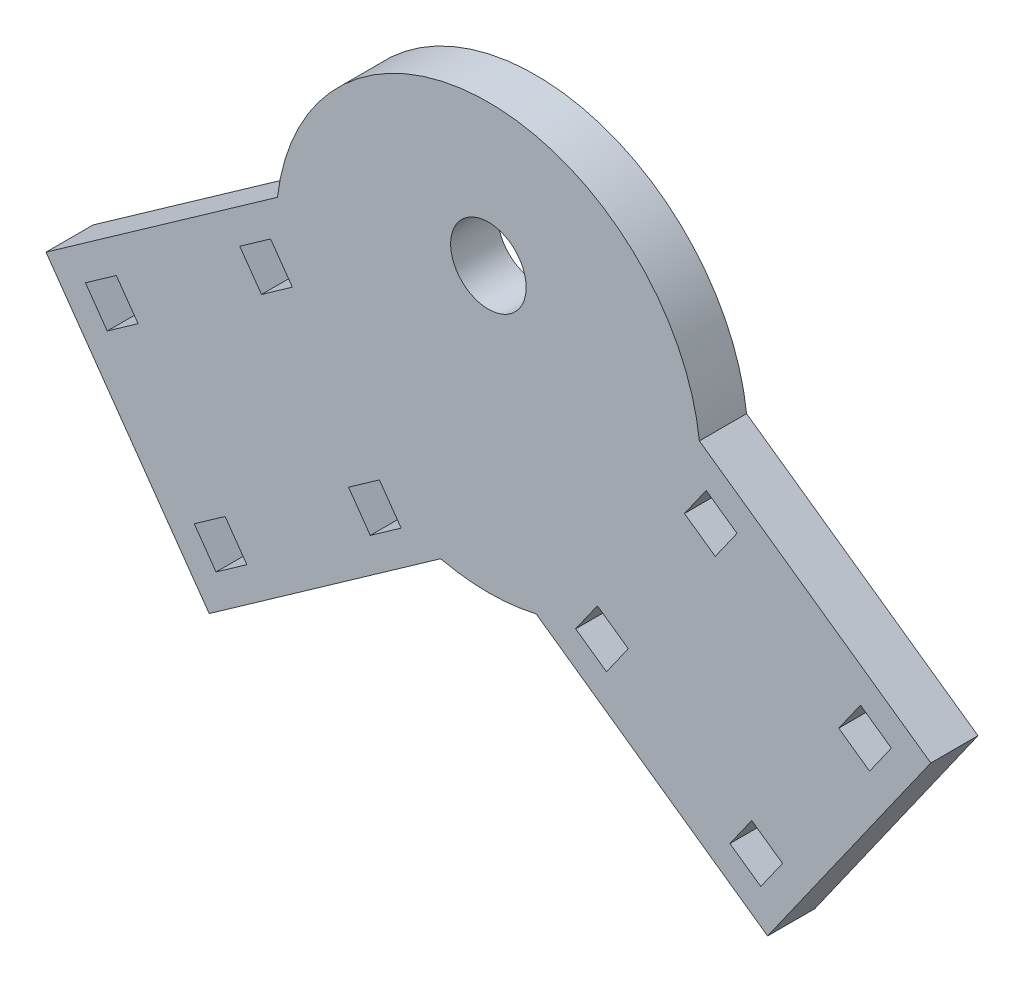
SolidWorks part; units mm, degrees
ref_plane "Front Plane" through (0, 0, 0) normal (0, 0, 1) x (1, 0, 0)
ref_plane "Top Plane" through (0, 0, 0) normal (0, 1, 0) x (1, 0, 0)
ref_plane "Right Plane" through (0, 0, 0) normal (1, 0, 0) x (0, 0, -1)
sketch "Sketch2" plane through (0, 0, 0) normal (0, 0, 1) x (1, 0, 0)
  line L8 (0, 0) -> (0, -22.5) construction
  line L9 (0, 0) -> (5.0614, -21.9233)
  line L10 (0, 0) -> (-5.0614, -21.9233)
  line L11 (5.0614, -21.9233) -> (22.35, 2.5941)
  line L12 (5.0614, -21.9233) -> (29.5789, -39.2119)
  line L13 (22.35, 2.5941) -> (46.8674, -14.6944)
  line L14 (29.5789, -39.2119) -> (46.8674, -14.6944)
  line L15 (-5.0614, -21.9233) -> (-22.35, 2.5941)
  line L16 (-5.0614, -21.9233) -> (-29.5789, -39.2119)
  line L17 (-22.35, 2.5941) -> (-46.8674, -14.6944)
  line L18 (-29.5789, -39.2119) -> (-46.8674, -14.6944)
  circle A0 centre (0, 0) radius 22.5
  circle A2 centre (0, 7.5) radius 4
  dimension "D5" = 45
  dimension "D1" = 13
  dimension "D2" = 13
  dimension "D3" = 30
  dimension "D4" = 30
  dimension "D6" = 30
  dimension "D7" = 30
extrude "Boss-Extrude1" add sketch "Sketch2" along normal blind 5 contours A0 | L15 L16 L18 L17 | L11 L12 L14 L13 | A2
sketch "Sketch4" plane through (0, 0, 5) normal (0, 0, 1) x (1, 0, 0)
  line L0 (-22.35, 2.5941) -> (-5.0614, -21.9233)
  line L1 (-22.35, 2.5941) -> (-46.8674, -14.6944) construction
  line L2 (-5.0614, -21.9233) -> (-29.5789, -39.2119) construction
  line L3 (-29.5789, -39.2119) -> (-46.8674, -14.6944) construction
  line L4 (5.0614, -21.9233) -> (22.35, 2.5941)
  line L5 (-39.8997, -15.8992) -> (-23.5548, -4.3735)
  line L6 (-23.5548, -4.3735) -> (-12.0291, -20.7185)
  line L7 (5.0614, -21.9233) -> (29.5789, -39.2119) construction
  line L8 (22.35, 2.5941) -> (46.8674, -14.6944) construction
  line L9 (29.5789, -39.2119) -> (46.8674, -14.6944) construction
  line L10 (-12.0291, -20.7185) -> (-28.374, -32.2442)
  line L11 (-28.374, -32.2442) -> (-39.8997, -15.8992)
  line L12 (-42.6868, -15.4173) -> (-39.4178, -13.1122)
  line L13 (-39.4178, -13.1122) -> (-37.1127, -16.3812)
  line L14 (-37.1127, -16.3812) -> (-40.3817, -18.6863)
  line L15 (-40.3817, -18.6863) -> (-42.6868, -15.4173)
  line L16 (-31.1611, -31.7623) -> (-27.8921, -29.4571)
  line L17 (-27.8921, -29.4571) -> (-25.587, -32.7261)
  line L18 (-25.587, -32.7261) -> (-28.856, -35.0313)
  line L19 (-28.856, -35.0313) -> (-31.1611, -31.7623)
  line L20 (-11.5471, -17.9314) -> (-14.8161, -20.2366)
  line L21 (-14.8161, -20.2366) -> (-12.511, -23.5056)
  line L22 (-12.511, -23.5056) -> (-9.242, -21.2004)
  line L23 (-9.242, -21.2004) -> (-11.5471, -17.9314)
  line L24 (-26.3418, -3.8916) -> (-23.0728, -1.5865)
  line L25 (-23.0728, -1.5865) -> (-20.7677, -4.8555)
  line L26 (-23.0728, -1.5865) -> (-20.7677, -4.8555) construction
  line L27 (-20.7677, -4.8555) -> (-24.0367, -7.1606) construction
  line L28 (-20.7677, -4.8555) -> (-24.0367, -7.1606)
  line L29 (-24.0367, -7.1606) -> (-26.3418, -3.8916)
  line L30 (23.5548, -4.3735) -> (39.8997, -15.8992)
  line L31 (39.8997, -15.8992) -> (28.374, -32.2442)
  line L32 (28.374, -32.2442) -> (12.0291, -20.7185)
  line L33 (12.0291, -20.7185) -> (23.5548, -4.3735)
  line L34 (23.0728, -1.5865) -> (26.3418, -3.8916)
  line L35 (26.3418, -3.8916) -> (24.0367, -7.1606)
  line L36 (20.7677, -4.8555) -> (24.0367, -7.1606) construction
  line L37 (24.0367, -7.1606) -> (20.7677, -4.8555)
  line L38 (20.7677, -4.8555) -> (23.0728, -1.5865)
  line L39 (37.1127, -16.3812) -> (39.4178, -13.1122)
  line L40 (39.4178, -13.1122) -> (42.6868, -15.4173)
  line L41 (42.6868, -15.4173) -> (40.3817, -18.6863)
  line L42 (40.3817, -18.6863) -> (37.1127, -16.3812)
  line L43 (27.8921, -29.4571) -> (31.1611, -31.7623)
  line L44 (31.1611, -31.7623) -> (28.856, -35.0313)
  line L45 (28.856, -35.0313) -> (25.587, -32.7261)
  line L46 (25.587, -32.7261) -> (27.8921, -29.4571)
  line L47 (11.5471, -17.9314) -> (14.8161, -20.2366)
  line L48 (11.5471, -17.9314) -> (14.8161, -20.2366) construction
  line L49 (14.8161, -20.2366) -> (12.511, -23.5056)
  line L50 (12.511, -23.5056) -> (9.242, -21.2004)
  line L51 (9.242, -21.2004) -> (11.5471, -17.9314)
  dimension "D1" = 30
  dimension "D2" = 5
  dimension "D3" = 5
  dimension "D4" = 5
  dimension "D5" = 5
  dimension "D6" = 5
  dimension "D7" = 5
  dimension "D8" = 5
  dimension "D9" = 5
  dimension "D14" = 30
  dimension "D15" = 5
  dimension "D16" = 5
  dimension "D17" = 5
  dimension "D18" = 5
  dimension "D21" = 5
  dimension "D22" = 5
  dimension "D23" = 5
  dimension "D24" = 5
extrude "Cut-Extrude1" cut sketch "Sketch4" against normal blind 10 contours L20 L21 L22 L23 | L13 L14 L15 L12 | L24 L25 L28 L29 | L17 L18 L19 L16 | L50 L51 L47 L49 | L34 L35 L37 L38 | L40 L41 L42 L39 | L43 L44 L45 L46
sketch "Sketch5" plane through (0, 0, 5) normal (0, 0, 1) x (1, 0, 0)
  line L0 (0, 22.5) -> (0, -22.5)
  arc A0 (22.35, 2.5941) -> (-22.35, 2.5941) centre (0, 0) ccw construction
  arc A1 (-5.0614, -21.9233) -> (5.0614, -21.9233) centre (0, 0) ccw construction
  circle A2 centre (0, 7.5) radius 4
  dimension "D2" = 8
  dimension "D1" = 15
